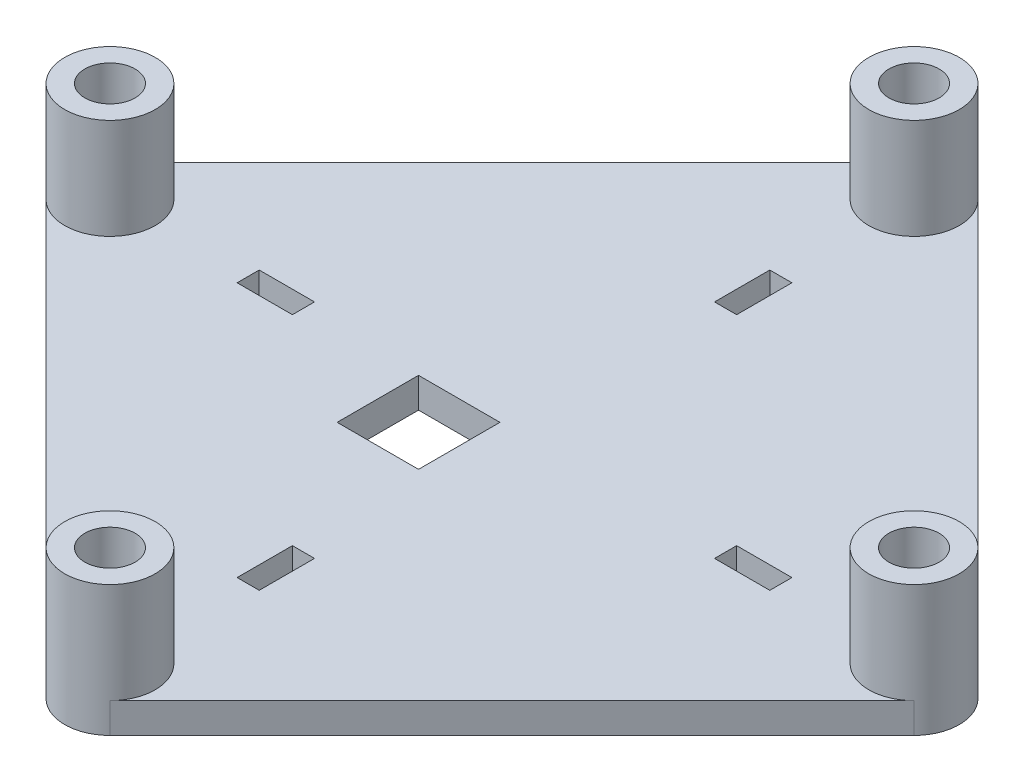
SolidWorks part; units mm, degrees
ref_plane "Front Plane" through (0, 0, 0) normal (0, 0, 1) x (1, 0, 0)
ref_plane "Top Plane" through (0, 0, 0) normal (0, 1, 0) x (1, 0, 0)
ref_plane "Right Plane" through (0, 0, 0) normal (1, 0, 0) x (0, 0, -1)
sketch "Sketch1" plane through (0, 0, 0) normal (0, 1, 0) x (1, 0, 0)
  line L1 (-50, -50) -> (50, -50)
  line L2 (-50, -50) -> (-50, 50)
  line L3 (-50, 50) -> (50, 50)
  line L4 (50, -50) -> (50, 50)
  line L5 (-50, -50) -> (50, 50) construction
  line L6 (-50, 50) -> (50, -50) construction
  point P0 (0, 0)
  dimension "D1" = 100
  dimension "D2" = 100
extrude "Boss-Extrude1" add sketch "Sketch1" along normal blind 3
sketch "Sketch2" plane through (0, 3, 0) normal (0, 1, 0) x (1, 0, 0)
  circle A0 centre (0, 40) radius 2.5
  circle A1 centre (0, 40) radius 4.5
  circle A2 centre (40, 0) radius 2.5
  circle A3 centre (40, 0) radius 4.5
  circle A4 centre (0, -40) radius 2.5
  circle A5 centre (0, -40) radius 4.5
  circle A6 centre (-40, 0) radius 2.5
  circle A7 centre (-40, 0) radius 4.5
  point P20 (0, 0)
  dimension "D1" = 40
  dimension "D2" = 2
  dimension "D3" = 4
extrude "Boss-Extrude2" add sketch "Sketch2" along normal blind 10
sketch "Sketch3" plane through (0, 3, 0) normal (0, 1, 0) x (1, 0, 0)
  line L0 (0, -24) -> (0, 24) construction
  line L1 (21, -0.85) -> (26.5, -0.85)
  line L2 (1.1, 21.25) -> (-1.1, 21.25)
  line L3 (1.1, 21.25) -> (1.1, 26.75)
  line L4 (1.1, 26.75) -> (-1.1, 26.75)
  line L5 (-1.1, 21.25) -> (-1.1, 26.75)
  line L6 (1.1, 21.25) -> (-1.1, 26.75) construction
  line L7 (1.1, 26.75) -> (-1.1, 21.25) construction
  line L8 (21, -0.85) -> (21, 1.35)
  line L9 (21, 1.35) -> (26.5, 1.35)
  line L10 (26.5, -0.85) -> (26.5, 1.35)
  line L11 (-1.1, -20.75) -> (-1.1, -26.25)
  line L12 (-1.1, -20.75) -> (1.1, -20.75)
  line L13 (1.1, -20.75) -> (1.1, -26.25)
  line L14 (-1.1, -26.25) -> (1.1, -26.25)
  line L15 (-21, 1.35) -> (-26.5, 1.35)
  line L16 (-21, 1.35) -> (-21, -0.85)
  line L17 (-21, -0.85) -> (-26.5, -0.85)
  line L18 (-26.5, 1.35) -> (-26.5, -0.85)
  point P22 (0, 0.25)
  dimension "D1" = 48
  dimension "D2" = 5.5
  dimension "D3" = 2.2
  dimension "D4" = 4
sketch "Sketch9" plane through (0, 3, 0) normal (0, 1, 0) x (1, 0, 0)
  line L0 (0, 0) -> (12.8806, -12.8806) construction
  line L1 (3.182, 43.182) -> (43.182, 3.182)
  line L2 (-3.182, 43.182) -> (-43.182, 3.182)
  line L3 (43.182, -3.182) -> (3.182, -43.182)
  line L4 (-43.182, -3.182) -> (-3.182, -43.182)
  line L5 (0, 46.364) -> (0, -46.364) construction
  line L6 (46.364, 0) -> (-46.364, 0) construction
  arc A0 (3.182, -43.182) -> (-3.182, -43.182) centre (0, -40) cw
  arc A1 (-43.182, 3.182) -> (-43.182, -3.182) centre (-40, 0) ccw
  arc A2 (-3.182, 43.182) -> (3.182, 43.182) centre (0, 40) cw
  arc A3 (43.182, 3.182) -> (43.182, -3.182) centre (40, 0) cw
  dimension "D1" = 4.5
  dimension "D2" = 4.5
extrude "Cut-Extrude5" cut sketch "Sketch9" against normal blind 127 flip side to cut
sketch3d "3DSketch2"
  line L0 (0, 0, 0) -> (0, 11.5021, 0) construction
ref_axis "Axis1" through (0, 0, 0) along (0, 1, 0)
sketch "Sketch11" plane through (0, 3, 0) normal (0, 1, 0) x (1, 0, 0)
  line L0 (0, 8) -> (7.3574, 8) construction
  line L1 (0, 9) -> (7.3574, 9) construction
  line L2 (-8, 0) -> (-8, 5.4915) construction
  line L3 (-8, 5.4915) -> (-11, 5.4915) construction
  line L4 (-11, 5.4915) -> (-11, -2.1607) construction
  line L5 (-9.5, 5.4915) -> (-9.5, -2.1607) construction
  line L6 (-9.5, 0.2) -> (8.1206, 0.2) construction
  line L8 (-9.5, 0.2) -> (-1.4, 0.2)
  line L9 (-9.5, 0.2) -> (-9.5, -7.9)
  line L10 (-9.5, -7.9) -> (-1.4, -7.9)
  line L11 (-1.4, 0.2) -> (-1.4, -7.9)
  dimension "D1" = 1
  dimension "D2" = 3
  dimension "D3" = 1.5
  dimension "D4" = 8.8
  dimension "D5" = 8.1
  dimension "D6" = 8.1
extrude "Cut-Extrude6" cut sketch "Sketch11" against normal blind 127
extrude "Cut-Extrude7" cut sketch "Sketch3" against normal through all
